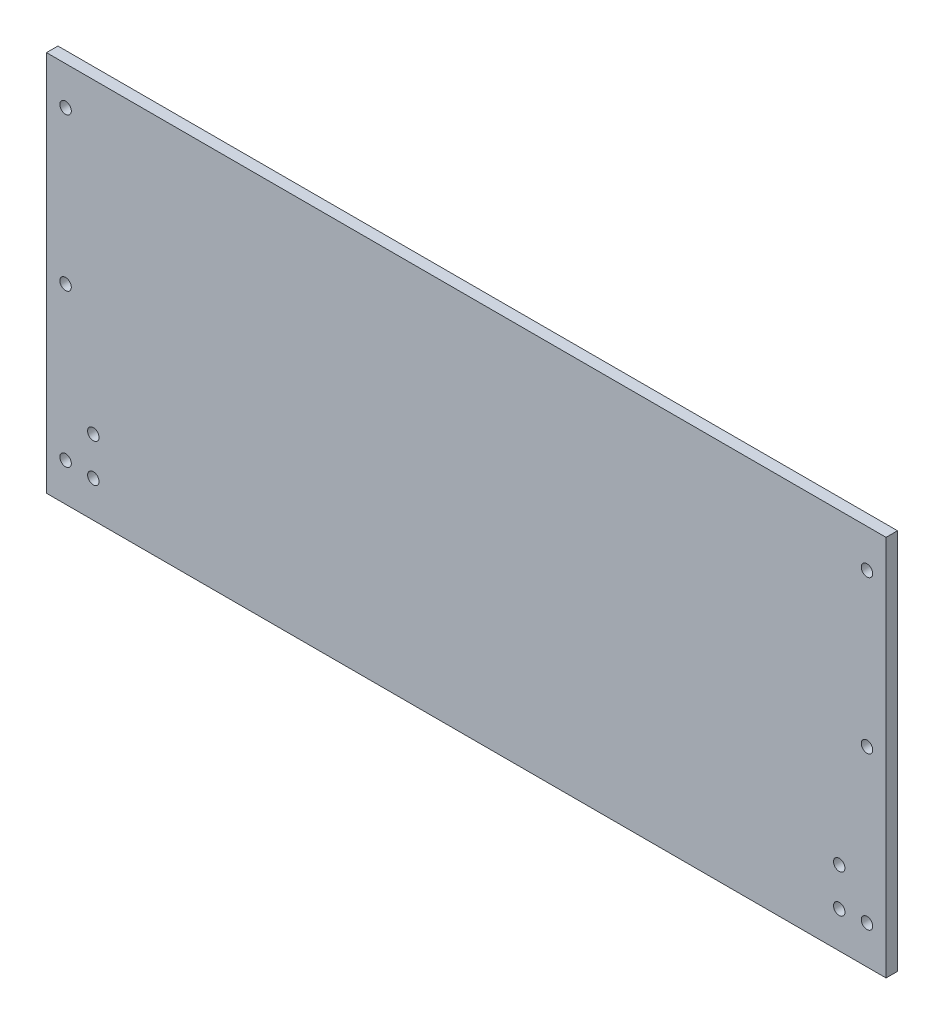
SolidWorks part; units mm, degrees
ref_plane "Plan de face" through (0, 0, 0) normal (0, 0, 1) x (1, 0, 0)
ref_plane "Plan de dessus" through (0, 0, 0) normal (0, 1, 0) x (1, 0, 0)
ref_plane "Plan de droite" through (0, 0, 0) normal (1, 0, 0) x (0, 0, -1)
sketch "Esquisse1" plane through (0, 0, 0) normal (0, 0, 1) x (1, 0, 0)
  line L0 (-105, -50) -> (-105, 50) construction
  line L1 (110, -50) -> (-110, -50)
  line L2 (110, -50) -> (110, 50)
  line L3 (110, 50) -> (-110, 50)
  line L4 (-110, -50) -> (-110, 50)
  line L5 (110, -50) -> (-110, 50) construction
  line L6 (110, 50) -> (-110, -50) construction
  line L7 (0, 50) -> (0, -50) construction
  circle A0 centre (-105, -40) radius 1.5
  circle A1 centre (-105, 0) radius 1.5
  circle A2 centre (-105, 40) radius 1.5
  circle A3 centre (105, 40) radius 1.5
  circle A4 centre (105, 0) radius 1.5
  circle A5 centre (105, -40) radius 1.5
  circle A6 centre (-97.7283, -30.4553) radius 1.5
  circle A10 centre (-97.7283, -40.4553) radius 1.5
  circle A11 centre (97.7283, -40.4553) radius 1.5
  circle A12 centre (97.7283, -30.4553) radius 1.5
  point P0 (0, 0)
  dimension "D4" = 3
  dimension "D8" = 3
  dimension "D9" = 3
  dimension "D1" = 220
  dimension "D2" = 100
  dimension "D3" = 5
  dimension "D5" = 10
  dimension "D7" = 10
  dimension "D6" = 3
extrude "Boss.-Extru.1" add sketch "Esquisse1" along normal blind 3
